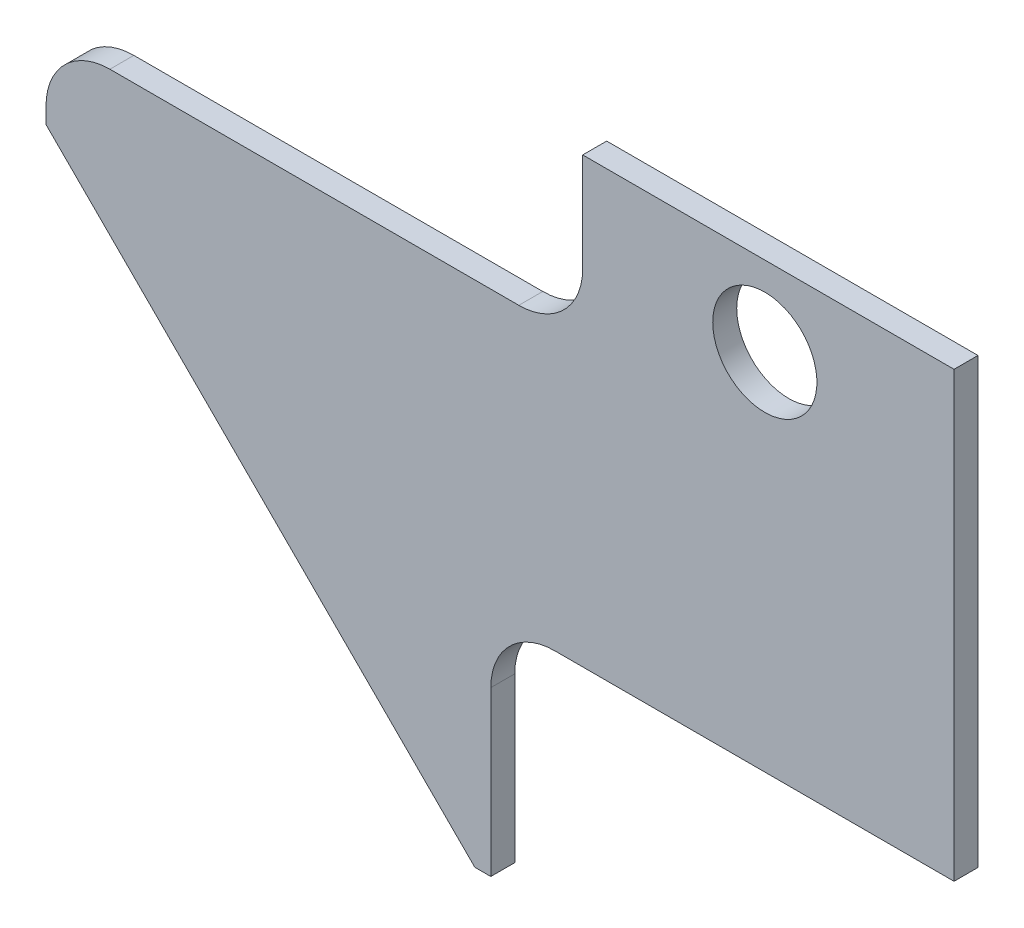
SolidWorks part; units mm, degrees
ref_plane "Front Plane" through (0, 0, 0) normal (0, 0, 1) x (1, 0, 0)
ref_plane "Top Plane" through (0, 0, 0) normal (0, 1, 0) x (1, 0, 0)
ref_plane "Right Plane" through (0, 0, 0) normal (1, 0, 0) x (0, 0, -1)
sketch "Sketch1" plane through (0, 0, 0) normal (0, 0, 1) x (1, 0, 0)
  line L0 (-138.2594, 48.9915) -> (32.2106, -121.4785)
  line L1 (32.2106, -121.4785) -> (222.7106, -121.4785)
  line L2 (-138.2594, 145.2215) -> (-138.2594, 48.9915)
  line L3 (-138.2594, 145.2215) -> (222.7106, 145.2215)
  line L4 (222.7106, -121.4785) -> (222.7106, 145.2215)
  circle A0 centre (147.4906, 113.4715) radius 20.701
  circle A2 centre (147.4906, 113.4715) radius 69.85 construction
  circle A3 centre (147.4906, 113.4715) radius 285.75 construction
  point P0 (0, 0)
  point P2 (147.4906, 113.4715)
  dimension "D4" = 234.95
  dimension "D1" = 45
  dimension "D2" = 266.7
  dimension "D5" = 247.65
extrude "Boss-Extrude1" add sketch "Sketch1" along normal blind 9.525
sketch "Sketch2" plane through (0, 0, 9.525) normal (0, 0, 1) x (1, 0, 0)
  line L0 (32.2106, -121.4785) -> (222.7106, -121.4785) construction
  line L1 (222.7106, -121.4785) -> (38.5606, -121.4785)
  line L2 (222.7106, -121.4785) -> (222.7106, -31.0571)
  line L3 (222.7106, -31.0571) -> (38.5606, -31.0571)
  line L4 (38.5606, -121.4785) -> (38.5606, -31.0571)
extrude "Cut-Extrude1" cut sketch "Sketch2" against normal through all contours L3 L4 L1 L2
fillet "Fillet1" radius 25.4 1 edges at (38.5606, -31.0571, 4.7625)
sketch "Sketch4" plane through (0, 0, 9.525) normal (0, 0, 1) x (1, 0, 0)
  line L1 (-138.2594, 145.2215) -> (-138.2594, 48.9915) construction
  line L3 (-138.2594, 145.2215) -> (75.1006, 145.2215)
  line L4 (-138.2594, 145.2215) -> (-138.2594, 80.7415)
  line L5 (-138.2594, 80.7415) -> (75.1006, 80.7415)
  line L6 (75.1006, 145.2215) -> (75.1006, 80.7415)
extrude "Cut-Extrude2" cut sketch "Sketch4" against normal through all contours L5 L6 L3 L4
fillet "Fillet2" radius 25.4 2 edges at (-138.2594, 80.7415, 4.7625) (75.1006, 80.7415, 4.7625)
